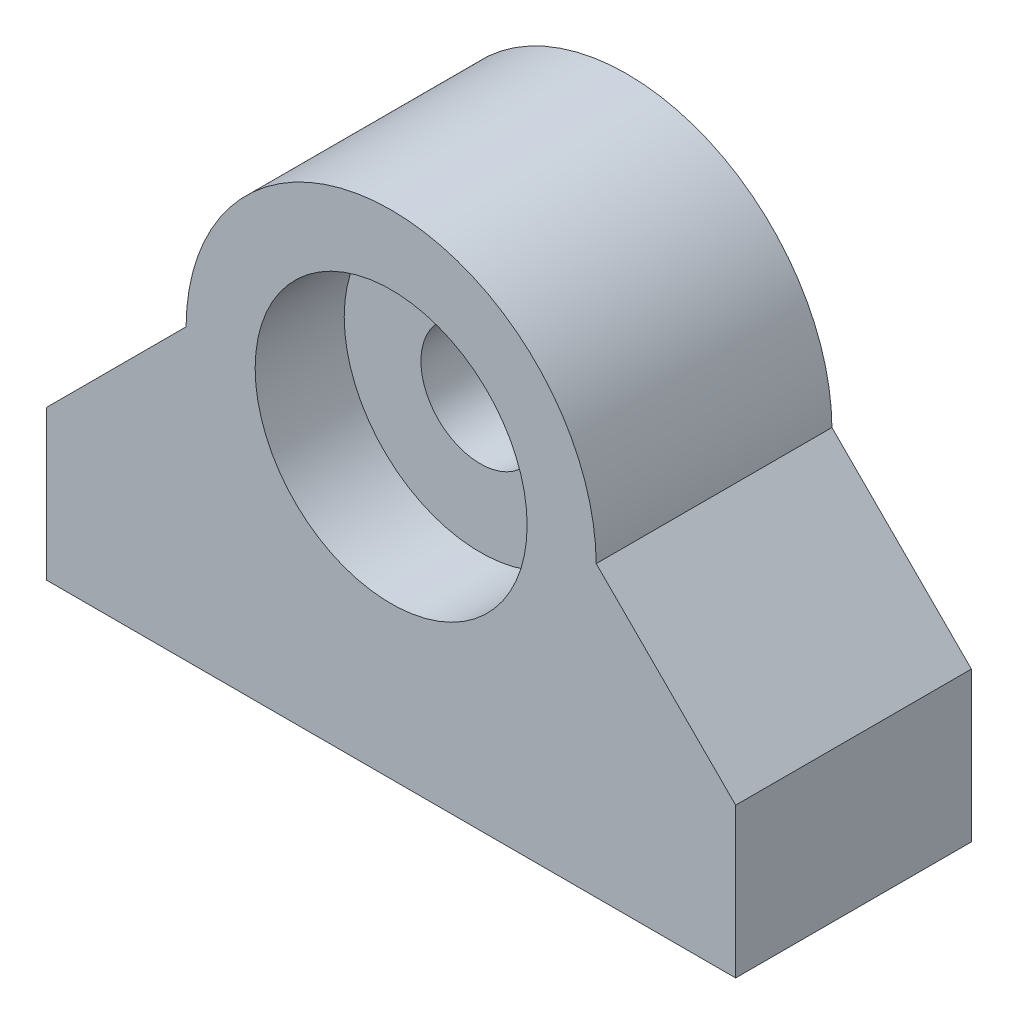
SolidWorks part; units mm, degrees
ref_plane "Front Plane" through (0, 0, 0) normal (0, 0, 1) x (1, 0, 0)
ref_plane "Top Plane" through (0, 0, 0) normal (0, 1, 0) x (1, 0, 0)
ref_plane "Right Plane" through (0, 0, 0) normal (1, 0, 0) x (0, 0, -1)
sketch "Sketch1" plane through (0, 0, 0) normal (0, 0, 1) x (1, 0, 0)
  line L0 (0, -26.1041) -> (0, 52.7781) construction
  line L3 (0, 0) -> (-19, 0)
  line L4 (19, 0) -> (19, 8.255)
  line L5 (19, 8.255) -> (11.3098, 15.9452)
  line L7 (-19, 0) -> (-19, 8.255)
  line L8 (0, 0) -> (19, 0)
  line L9 (-19, 8.255) -> (-11.3098, 15.9452)
  circle A0 centre (0, 15.874) radius 7.5
  arc A1 (-11.3098, 15.9452) -> (11.3098, 15.9452) centre (0, 15.874) cw
  point P11 (0, 4.699)
  point P12 (0, 28.448)
  point P15 (0, 8.374)
  dimension "D6" = 15
  dimension "D3" = 3.81
  dimension "D1" = 8.255
  dimension "D4" = 45
  dimension "D5" = 15.874
  dimension "D7" = 38
extrude "Boss-Extrude1" add sketch "Sketch1" along normal blind 13
ref_plane "Plane1" through (0, 0, 6.5) normal (0, 0, 1) x (1, 0, 0)
sketch "Sketch3" plane through (0, 0, 6.5) normal (0, 0, 1) x (1, 0, 0)
  circle A0 centre (0, 15.874) radius 3.2703
  circle A1 centre (0, 15.874) radius 8.7376
  dimension "D1" = 6.5405
  dimension "D2" = 17.4752
extrude "Boss-Extrude2" add sketch "Sketch3" along normal blind 1.5875 and the other way blind 1.5875
sketch "Sketch7" plane through (0, 0, 0) normal (0, -1, 0) x (1, 0, 0)
  line L0 (-19, 13) -> (19, 0) construction
  line L1 (0, 0) -> (0, 13) construction
  line L2 (-19, 13) -> (19, 13) construction
  point P9 (0, 6.5)
hole_wizard "M4x0.7 Tapped Hole1" positions "Sketch5" profile "Sketch6" tap size "M4x0.7" standard "ANSI Metric"
sketch "Sketch5" plane through (0, 0, 0) normal (0, -1, 0) x (-1, 0, 0)
  point P0 (10, -6.5)
  point P2 (-10, -6.5)
  dimension "D1" = 10
  dimension "D2" = 0
  dimension "D3" = 10
  dimension "D4" = 0
sketch "Sketch6" plane through (-10, 0, 6.5) normal (1, 0, 0) x (0, 0, -1)
  line L0 (0, 0) -> (0, 11.1006)
  line L1 (0, 11.1006) -> (1.65, 10.1092)
  line L2 (1.65, 10.1092) -> (1.65, 0)
  line L5 (1.65, 0) -> (0, 0)
  line L10 (0, 11.1006) -> (-1.65, 10.1092) construction
  line L11 (0, -6.35) -> (0, 107.95) construction
  dimension "Tap Drill Dia." = 3.3
  dimension "Tap Drill Depth" = 10.1092
  dimension "Drill Angle" = 118
cosmetic thread "Hole Thread1" parameters "D1"=8.001, "D2"=4
cosmetic thread "Hole Thread2" parameters "D1"=8.001, "D2"=4
equation "\"0.095inin\"=0.085"
